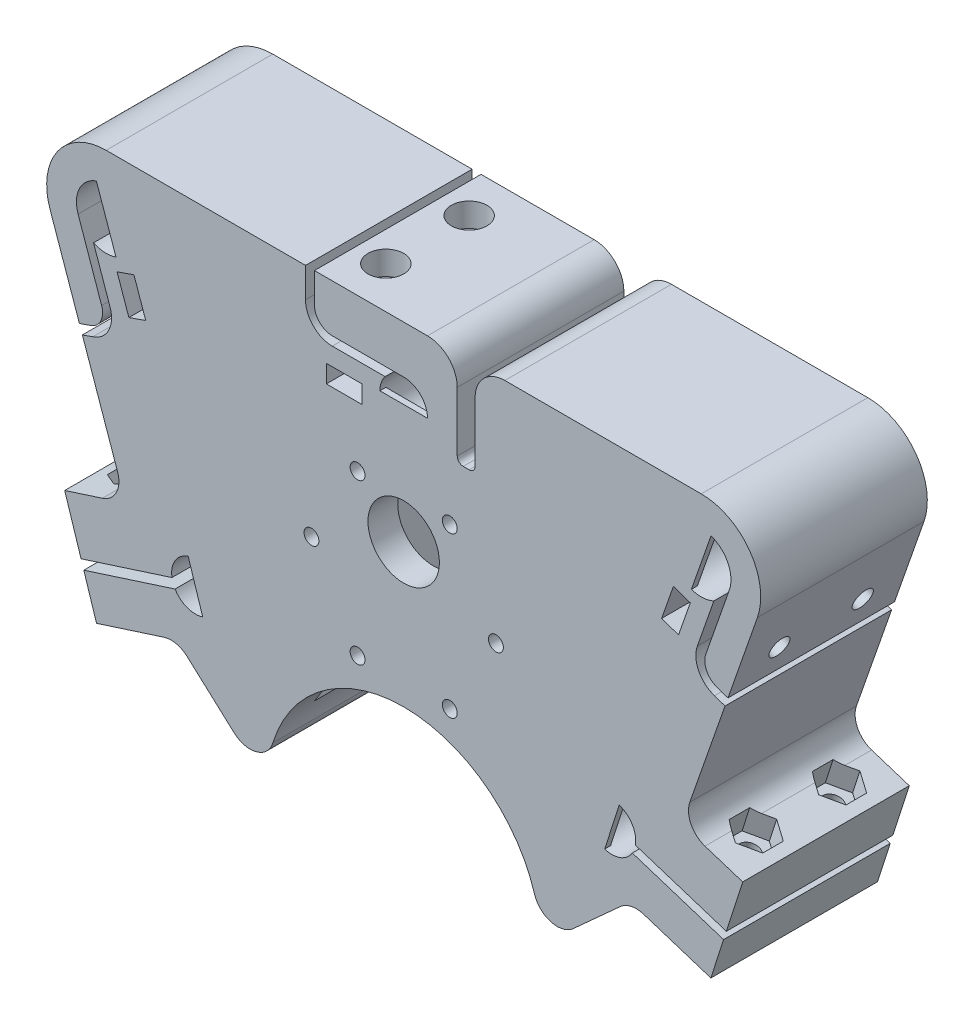
SolidWorks part; units mm, degrees
other "Uwaga1"
sketch "Szkic11" plane through (60, 10, 0) normal (0.4049, 0.0419, -0.9134) x (0.8662, -0.3375, 0.3685)
other "Uwaga2"
sketch "Szkic12" plane through (60, 10, 0) normal (0.4049, 0.0419, -0.9134) x (0.8662, -0.3375, 0.3685)
other "Uwaga3"
sketch "Szkic13"
ref_plane "Płaszczyzna przednia" through (0, 0, 0) normal (0, 0, 1) x (1, 0, 0)
ref_plane "Płaszczyzna górna" through (0, 0, 0) normal (0, 1, 0) x (1, 0, 0)
ref_plane "Płaszczyzna prawa" through (0, 0, 0) normal (1, 0, 0) x (0, 0, -1)
sketch "Szkic1" plane through (0, 0, 0) normal (0, 0, 1) x (1, 0, 0)
  line L0 (-50, 10) -> (4, 10)
  line L1 (-59.4412, -3.296) -> (-43.4971, -48.9664)
  line L2 (43.4971, -48.9664) -> (59.4412, -3.296)
  line L3 (-41.0394, -52.6727) -> (-23, -69)
  line L4 (23, -69) -> (41.0394, -52.6727)
  line L5 (38.4257, -48.0651) -> (43.2433, -49.6122)
  line L6 (38.9457, -46.6566) -> (43.7633, -48.2037)
  line L7 (0, -34.7604) -> (35, -46) construction
  line L8 (38.1168, -55.318) -> (51.621, -59.6546)
  line L9 (51.621, -59.6546) -> (53.7613, -52.9898)
  line L10 (53.7613, -52.9898) -> (43.2433, -49.6122)
  line L11 (43.7633, -48.2037) -> (54.2199, -51.5616)
  line L12 (54.2199, -51.5616) -> (56.9717, -42.9926)
  line L13 (56.9717, -42.9926) -> (46.7307, -39.704)
  line L14 (0, -29) -> (0, -114.3862) construction
  line L15 (0, 2) -> (-12, 2)
  line L16 (-3.1225, 0.5) -> (-12, 0.5)
  line L17 (-16.5, 5) -> (-16.5, 10)
  line L18 (-15, 5) -> (-15, 10)
  line L19 (9, 5) -> (9, -5)
  line L20 (10, -6) -> (11, -6)
  line L21 (12, -5) -> (12, 5)
  line L22 (17, 10) -> (50, 10)
  line L23 (-56.9717, -42.9926) -> (-46.7307, -39.704)
  line L24 (-54.2199, -51.5616) -> (-56.9717, -42.9926)
  line L25 (-43.7633, -48.2037) -> (-54.2199, -51.5616)
  line L26 (-38.9457, -46.6566) -> (-43.7633, -48.2037)
  line L27 (-38.4257, -48.0651) -> (-43.2433, -49.6122)
  line L28 (-53.7613, -52.9898) -> (-43.2433, -49.6122)
  line L29 (-51.621, -59.6546) -> (-53.7613, -52.9898)
  line L30 (-38.1168, -55.318) -> (-51.621, -59.6546)
  line L31 (-54.7206, -1.648) -> (-50.7653, -12.9775)
  line L32 (-52.1248, -4.5261) -> (-49.3471, -12.4823)
  line L33 (-52.6089, -16.7986) -> (-54.4971, -17.4578)
  line L34 (-52.2456, -18.2606) -> (-54.0027, -18.874)
  line L35 (54.7206, -1.648) -> (50.7653, -12.9775)
  line L36 (52.1248, -4.5261) -> (49.3471, -12.4823)
  line L37 (52.6089, -16.7986) -> (54.4971, -17.4578)
  line L38 (52.2456, -18.2606) -> (54.0027, -18.874)
  circle A0 centre (-50, 0) radius 5
  circle A1 centre (50, 0) radius 5
  circle A2 centre (-50, 0) radius 10
  circle A3 centre (50, 0) radius 10
  circle A4 centre (0, -2) radius 4
  circle A5 centre (0, -29) radius 15.5 construction
  circle A6 centre (0, -22) radius 6
  circle A7 centre (15.5, -29) radius 1.25
  circle A8 centre (7.75, -42.4234) radius 1.25
  circle A9 centre (-7.75, -42.4234) radius 1.25
  circle A10 centre (-15.5, -29) radius 1.25
  circle A11 centre (-7.75, -15.5766) radius 1.25
  circle A12 centre (7.75, -15.5766) radius 1.25
  circle A13 centre (-35, -46) radius 4
  circle A14 centre (35, -46) radius 4
  circle A15 centre (-35, -46) radius 9
  circle A16 centre (35, -46) radius 9
  arc A17 (23, -69) -> (-23, -69) centre (0, -69) ccw
  arc A19 (-12, 2) -> (-15, 5) centre (-12, 5) cw
  arc A20 (-12, 0.5) -> (-16.5, 5) centre (-12, 5) cw
  arc A21 (9, 5) -> (4, 10) centre (4, 5) ccw
  arc A22 (12, 5) -> (17, 10) centre (17, 5) cw
  arc A23 (11, -6) -> (12, -5) centre (11, -5) ccw
  arc A24 (9, -5) -> (10, -6) centre (10, -5) ccw
  arc A25 (-50.7653, -12.9775) -> (-52.6089, -16.7986) centre (-53.5977, -13.9663) cw
  arc A26 (-49.3471, -12.4823) -> (-52.2456, -18.2606) centre (-53.5977, -13.9663) cw
  arc A27 (49.3471, -12.4823) -> (52.2456, -18.2606) centre (53.5977, -13.9663) ccw
  arc A28 (50.7653, -12.9775) -> (52.6089, -16.7986) centre (53.5977, -13.9663) ccw
  point P32 (0, -29)
  point P78 (10.1421, 10)
  point P84 (10.1421, -2)
  point P87 (7.1421, -2)
  point P103 (-49.7765, -15.8098)
  dimension "D1" = 10
  dimension "D6" = 8
  dimension "D8" = 31
  dimension "D9" = 12
  dimension "D12" = 2.5
  dimension "D14" = 70
  dimension "D18" = 46
  dimension "D27" = 3
  dimension "D28" = 4.5
  dimension "D31" = 5
  dimension "D32" = 5
  dimension "D33" = 1
  dimension "D38" = 3
  dimension "D2" = 100
  dimension "D3" = 50
  dimension "D7" = 39
  dimension "D10" = 7
  dimension "D11" = 12
  dimension "D15" = 35
  dimension "D16" = 46
  dimension "D19" = 40
  dimension "D20" = 1.5
  dimension "D21" = 7
  dimension "D22" = 20
  dimension "D23" = 9
  dimension "D24" = 1.5
  dimension "D25" = 1.5
  dimension "D26" = 15
  dimension "D29" = 3
  dimension "D30" = 16
  dimension "D34" = 9
  dimension "D35" = 15
  dimension "D36" = 1.5021
  dimension "D37" = 1.5
  dimension "D4" = 5
  dimension "D5" = 5
  dimension "D17" = 5
  dimension "D13" = 6
extrude "Dodanie-wyciągnięcie1" add sketch "Szkic1" along normal blind 28 contours A2 A0 | A17 L4 A16 L2 A3 L0 A2 L1 A15 L3 A12 A11 A10 A9 A8 A7 A6 A4 | A3 A1 | A16 A14 | A15 A13 | A16 L4 L8 L9 L10 | L12 L13 L2 L11 | A15 L28 L29 L30 L3 | L25 L1 L23 L24 | A25 L31 A2 L1 L33 | L35 A28 L37 L2 A3 region at (-33.25, 8.6619, 0) region at (-43.1289, 6.8711, 0) region at (-54.1165, -12.2056, 0) region at (-50.4165, -45.6303, 0) region at (-36.0734, -37.3207, 0) region at (-46.741, -54.5771, 0) region at (56.8711, 6.8711, 0) region at (46.741, -54.5771, 0) region at (54.1165, -12.2056, 0) region at (27.0061, -42.4532, 0) region at (50.4165, -45.6303, 0)
fillet "Zaokrąglenie1" radius 4 6 edges at (-46.7307, -39.704, 14) (-38.1168, -55.318, 14) (-23, -69, 14) (23, -69, 14) (38.1168, -55.318, 14) (46.7307, -39.704, 14)
sketch "Szkic2" plane through (12.5403, -39.0504, 0) normal (0.3058, -0.9521, 0) x (0.9521, 0.3058, 0)
  line L0 (-55.5122, 28) -> (-67.3885, 28) construction
  line L1 (-67.3885, 28) -> (-67.3885, 0) construction
  circle A0 centre (-62.3885, 21) radius 1.7
  circle A1 centre (-62.3885, 7) radius 1.7
  dimension "D1" = 14
  dimension "D4" = 3.4
  dimension "D2" = 7
  dimension "D3" = 5
extrude "Wytnij-wyciągnięcie1" cut sketch "Szkic2" against normal through all
sketch "Szkic3" plane through (12.5403, -39.0504, 0) normal (0.3058, -0.9521, 0) x (0.9521, 0.3058, 0)
  circle A0 centre (-62.3885, 21) radius 3
  circle A1 centre (-62.3885, 7) radius 3
  dimension "D1" = 6
extrude "Wytnij-wyciągnięcie2" cut sketch "Szkic3" against normal blind 3
sketch "Szkic4" plane through (7.1896, -22.3885, 0) normal (-0.3058, 0.9521, 0) x (0.9521, 0.3058, 0)
  line L1 (-62.3885, -24.4641) -> (-59.3885, -22.7321)
  line L2 (-59.3885, -22.7321) -> (-59.3885, -19.2679)
  line L3 (-59.3885, -19.2679) -> (-62.3885, -17.5359)
  line L4 (-62.3885, -17.5359) -> (-65.3885, -19.2679)
  line L5 (-65.3885, -19.2679) -> (-65.3885, -22.7321)
  line L6 (-65.3885, -22.7321) -> (-62.3885, -24.4641)
  line L7 (-62.3885, -10.4641) -> (-59.3885, -8.7321)
  line L8 (-59.3885, -8.7321) -> (-59.3885, -5.2679)
  line L9 (-59.3885, -5.2679) -> (-62.3885, -3.5359)
  line L10 (-62.3885, -3.5359) -> (-65.3885, -5.2679)
  line L11 (-65.3885, -5.2679) -> (-65.3885, -8.7321)
  line L12 (-65.3885, -8.7321) -> (-62.3885, -10.4641)
  circle A0 centre (-62.3885, -21) radius 3 construction
  circle A1 centre (-62.3885, -7) radius 3 construction
  dimension "D1" = 6
extrude "Wytnij-wyciągnięcie3" cut sketch "Szkic4" against normal blind 4 and the other way blind 4
sketch "Szkic5" plane through (-54.0092, -18.8553, 0) normal (-0.9441, -0.3296, 0) x (0, 0, 1)
  line L0 (28, 16.4802) -> (28, 1.4802) construction
  line L1 (28, 1.4802) -> (0, 1.4802) construction
  circle A0 centre (21, 6.4802) radius 1.7
  circle A1 centre (7, 6.4802) radius 1.7
  dimension "D1" = 14
  dimension "D2" = 3.4
  dimension "D3" = 7
  dimension "D4" = 5
extrude "Wytnij-wyciągnięcie4" cut sketch "Szkic5" against normal blind 10
sketch "Szkic6" plane through (-54.0092, -18.8553, 0) normal (-0.9441, -0.3296, 0) x (0, 0, 1)
  line L0 (22.7321, 9.4802) -> (28, 9.4802)
  line L1 (24.4641, 6.4802) -> (22.7321, 9.4802)
  line L2 (22.7321, 9.4802) -> (19.2679, 9.4802)
  line L3 (19.2679, 9.4802) -> (17.5359, 6.4802)
  line L4 (17.5359, 6.4802) -> (19.2679, 3.4802)
  line L5 (19.2679, 3.4802) -> (22.7321, 3.4802)
  line L6 (22.7321, 3.4802) -> (24.4641, 6.4802)
  line L7 (10.4641, 6.4802) -> (8.7321, 9.4802)
  line L8 (8.7321, 9.4802) -> (5.2679, 9.4802)
  line L9 (5.2679, 9.4802) -> (3.5359, 6.4802)
  line L10 (3.5359, 6.4802) -> (5.2679, 3.4802)
  line L11 (5.2679, 3.4802) -> (8.7321, 3.4802)
  line L12 (8.7321, 3.4802) -> (10.4641, 6.4802)
  line L13 (28, 16.4802) -> (28, 1.4802) construction
  line L14 (28, 9.4802) -> (28, 3.4802)
  line L15 (28, 3.4802) -> (22.7321, 3.4802)
  line L16 (5.2679, 9.4802) -> (0, 9.4802)
  line L17 (0, 16.4802) -> (0, 1.4802) construction
  line L18 (0, 9.4802) -> (0, 3.4802)
  line L19 (0, 3.4802) -> (5.2679, 3.4802)
  circle A0 centre (21, 6.4802) radius 3 construction
  circle A1 centre (7, 6.4802) radius 3 construction
  circle M2 centre (21, 6.4802) radius 1.7
  circle M3 centre (7, 6.4802) radius 1.7
  line M4 (0, 16.4802) -> (0, 1.4802)
  line M6 (28, 1.4802) -> (28, 16.4802)
  dimension "D1" = 6
extrude "Wytnij-wyciągnięcie5" cut sketch "Szkic6" against normal blind 3 from offset 9.5 contours L5 L6 L1 L2 L3 L4 M2 | L15 L0 L1 L6 M6 | L19 L10 L9 L16 M4 | L11 L12 L7 L8 L9 L10 M3 | M2 | M3 region at (-56.1452, -12.7372, 25.7706) region at (-56.6245, -11.3643, 23.5187) region at (-55.6658, -14.1101, 9.5187) region at (-56.1452, -12.7372, 2.2294) region at (-56.1452, -12.7372, 21) region at (-56.1452, -12.7372, 7) offset against normal yes
mirror "Lustro1" about plane through (0, 0, 0) normal (1, 0, 0) of "Wytnij-wyciągnięcie5", "Wytnij-wyciągnięcie4", "Wytnij-wyciągnięcie2", "Wytnij-wyciągnięcie1", "Wytnij-wyciągnięcie3"
sketch "Szkic7" plane through (0, 10, 0) normal (0, 1, 0) x (1, 0, 0)
  line L0 (-15, 0) -> (4, 0) construction
  line L1 (-15, -28) -> (-15, 0) construction
  circle A0 centre (-10, -21) radius 1.7
  circle A1 centre (-10, -7) radius 1.7
  point P4 (0, 0)
  point P5 (0, 0)
  point P6 (0, 0)
  dimension "D1" = 3.4
  dimension "D2" = 14
  dimension "D3" = 7
  dimension "D4" = 5
extrude "Wytnij-wyciągnięcie6" cut sketch "Szkic7" against normal blind 14
sketch "Szkic8" plane through (0, 10, 0) normal (0, 1, 0) x (1, 0, 0)
  line L0 (-7, -22.7321) -> (-7, -28)
  line L1 (-10, -24.4641) -> (-7, -22.7321)
  line L2 (-7, -22.7321) -> (-7, -19.2679)
  line L3 (-7, -19.2679) -> (-10, -17.5359)
  line L4 (-10, -17.5359) -> (-13, -19.2679)
  line L5 (-13, -19.2679) -> (-13, -22.7321)
  line L6 (-13, -22.7321) -> (-10, -24.4641)
  line L7 (-10, -10.4641) -> (-7, -8.7321)
  line L8 (-7, -8.7321) -> (-7, -5.2679)
  line L9 (-7, -5.2679) -> (-10, -3.5359)
  line L10 (-10, -3.5359) -> (-13, -5.2679)
  line L11 (-13, -5.2679) -> (-13, -8.7321)
  line L12 (-13, -8.7321) -> (-10, -10.4641)
  line L13 (-15, -28) -> (4, -28) construction
  line L14 (-7, -28) -> (-13, -28)
  line L15 (-13, -28) -> (-13, -22.7321)
  line L16 (-7, -5.2679) -> (-7, 0)
  line L17 (-15, 0) -> (4, 0) construction
  line L18 (-7, 0) -> (-13, 0)
  line L19 (-13, 0) -> (-13, -5.2679)
  circle A0 centre (-10, -21) radius 3 construction
  circle A1 centre (-10, -7) radius 3 construction
  circle M1 centre (-10, -21) radius 1.7
  circle M2 centre (-10, -7) radius 1.7
  line M3 (4, 0) -> (-15, 0)
  line M5 (-15, -28) -> (4, -28)
  dimension "D1" = 6
extrude "Wytnij-wyciągnięcie7" cut sketch "Szkic8" against normal blind 3 from offset 12.5 contours L5 L6 L1 L2 L3 L4 M1 | M1 | L15 L0 L1 L6 M5 | M2 | L11 L12 L7 L8 L9 L10 M2 | L19 L10 L9 L16 M3 region at (-10, 10, 25.7706) region at (-8.5458, 10, 23.5187) region at (-11.4542, 10, 9.5187) region at (-10, 10, 2.2294) region at (-10, 10, 21) region at (-10, 10, 7) offset against normal yes
sketch "Szkic9" plane through (0, 0, 28) normal (0, 0, 1) x (1, 0, 0)
  line L0 (-36.223, -42.1916) -> (-33.777, -49.8084)
  line L1 (36.223, -42.1916) -> (33.777, -49.8084)
  line L2 (-51.648, 4.7206) -> (-48.352, -4.7206)
  line L3 (51.648, 4.7206) -> (48.352, -4.7206)
  line L4 (-4, -2) -> (4, -2)
  line L36 (-36.4063, -56.8662) -> (-28.4915, -64.0297)
  line L37 (28.4915, -64.0297) -> (36.4063, -56.8662)
  line L38 (40.3135, -56.0234) -> (51.621, -59.6546)
  line L39 (51.621, -59.6546) -> (53.7613, -52.9898)
  line L40 (53.7613, -52.9898) -> (38.4257, -48.0651)
  line L41 (38.9457, -46.6566) -> (54.2199, -51.5616)
  line L42 (54.2199, -51.5616) -> (56.9717, -42.9926)
  line L43 (56.9717, -42.9926) -> (50.6362, -40.9581)
  line L44 (48.0827, -35.8313) -> (54.0027, -18.874)
  line L45 (54.0027, -18.874) -> (52.2456, -18.2606)
  line L46 (49.3471, -12.4823) -> (52.1248, -4.5261)
  line L47 (54.7206, -1.648) -> (50.7653, -12.9775)
  line L48 (52.6089, -16.7986) -> (54.4971, -17.4578)
  line L49 (54.4971, -17.4578) -> (59.4412, -3.296)
  line L50 (50, 10) -> (17, 10)
  line L51 (12, 5) -> (12, -5)
  line L52 (11, -6) -> (10, -6)
  line L53 (9, -5) -> (9, 5)
  line L54 (4, 10) -> (-15, 10)
  line L55 (-15, 10) -> (-15, 5)
  line L56 (-12, 2) -> (0, 2)
  line L57 (-3.1225, 0.5) -> (-12, 0.5)
  line L58 (-16.5, 5) -> (-16.5, 10)
  line L59 (-16.5, 10) -> (-50, 10)
  line L60 (-59.4412, -3.296) -> (-54.4971, -17.4578)
  line L61 (-54.4971, -17.4578) -> (-52.6089, -16.7986)
  line L62 (-50.7653, -12.9775) -> (-54.7206, -1.648)
  line L63 (-52.1248, -4.5261) -> (-49.3471, -12.4823)
  line L64 (-52.2456, -18.2606) -> (-54.0027, -18.874)
  line L65 (-54.0027, -18.874) -> (-48.0827, -35.8313)
  line L66 (-50.6362, -40.9581) -> (-56.9717, -42.9926)
  line L67 (-56.9717, -42.9926) -> (-54.2199, -51.5616)
  line L68 (-54.2199, -51.5616) -> (-38.9457, -46.6566)
  line L69 (-38.4257, -48.0651) -> (-53.7613, -52.9898)
  line L70 (-53.7613, -52.9898) -> (-51.621, -59.6546)
  line L71 (-51.621, -59.6546) -> (-40.3135, -56.0234)
  line L72 (-36.4063, -56.8662) -> (-28.4915, -64.0297)
  line L73 (28.4915, -64.0297) -> (36.4063, -56.8662)
  line L74 (40.3135, -56.0234) -> (51.621, -59.6546)
  line L75 (51.621, -59.6546) -> (53.7613, -52.9898)
  line L76 (53.7613, -52.9898) -> (38.4257, -48.0651)
  line L77 (38.9457, -46.6566) -> (54.2199, -51.5616)
  line L78 (54.2199, -51.5616) -> (56.9717, -42.9926)
  line L79 (56.9717, -42.9926) -> (50.6362, -40.9581)
  line L80 (48.0827, -35.8313) -> (54.0027, -18.874)
  line L81 (54.0027, -18.874) -> (52.2456, -18.2606)
  line L82 (49.3471, -12.4823) -> (52.1248, -4.5261)
  line L83 (54.7206, -1.648) -> (50.7653, -12.9775)
  line L84 (52.6089, -16.7986) -> (54.4971, -17.4578)
  line L85 (54.4971, -17.4578) -> (59.4412, -3.296)
  line L86 (50, 10) -> (17, 10)
  line L87 (12, 5) -> (12, -5)
  line L88 (11, -6) -> (10, -6)
  line L89 (9, -5) -> (9, 5)
  line L90 (4, 10) -> (-15, 10)
  line L91 (-15, 10) -> (-15, 5)
  line L92 (-12, 2) -> (0, 2)
  line L93 (-3.1225, 0.5) -> (-12, 0.5)
  line L94 (-16.5, 5) -> (-16.5, 10)
  line L95 (-16.5, 10) -> (-50, 10)
  line L96 (-59.4412, -3.296) -> (-54.4971, -17.4578)
  line L97 (-54.4971, -17.4578) -> (-52.6089, -16.7986)
  line L98 (-50.7653, -12.9775) -> (-54.7206, -1.648)
  line L99 (-52.1248, -4.5261) -> (-49.3471, -12.4823)
  line L100 (-52.2456, -18.2606) -> (-54.0027, -18.874)
  line L101 (-54.0027, -18.874) -> (-48.0827, -35.8313)
  line L102 (-50.6362, -40.9581) -> (-56.9717, -42.9926)
  line L103 (-56.9717, -42.9926) -> (-54.2199, -51.5616)
  line L104 (-54.2199, -51.5616) -> (-38.9457, -46.6566)
  line L105 (-38.4257, -48.0651) -> (-53.7613, -52.9898)
  line L106 (-53.7613, -52.9898) -> (-51.621, -59.6546)
  line L107 (-51.621, -59.6546) -> (-40.3135, -56.0234)
  arc A24 (-28.4915, -64.0297) -> (-21.984, -62.2397) centre (-25.8074, -61.064) ccw
  arc A25 (21.984, -62.2397) -> (-21.984, -62.2397) centre (0, -69) ccw
  arc A26 (21.984, -62.2397) -> (28.4915, -64.0297) centre (25.8074, -61.064) ccw
  arc A27 (40.3135, -56.0234) -> (36.4063, -56.8662) centre (39.0904, -59.8318) ccw
  arc A28 (38.9457, -46.6566) -> (38.4257, -48.0651) centre (35, -46) ccw
  arc A29 (48.0827, -35.8313) -> (50.6362, -40.9581) centre (51.8592, -37.1497) ccw
  arc A30 (49.3471, -12.4823) -> (52.2456, -18.2606) centre (53.5977, -13.9663) ccw
  arc A31 (54.7206, -1.648) -> (52.1248, -4.5261) centre (50, 0) ccw
  arc A32 (50.7653, -12.9775) -> (52.6089, -16.7986) centre (53.5977, -13.9663) ccw
  arc A33 (59.4412, -3.296) -> (50, 10) centre (50, 0) ccw
  arc A34 (17, 10) -> (12, 5) centre (17, 5) ccw
  arc A35 (11, -6) -> (12, -5) centre (11, -5) ccw
  arc A36 (9, -5) -> (10, -6) centre (10, -5) ccw
  arc A37 (9, 5) -> (4, 10) centre (4, 5) ccw
  arc A38 (-15, 5) -> (-12, 2) centre (-12, 5) ccw
  arc A39 (-3.1225, 0.5) -> (0, 2) centre (0, -2) ccw
  arc A40 (-16.5, 5) -> (-12, 0.5) centre (-12, 5) ccw
  arc A41 (-50, 10) -> (-59.4412, -3.296) centre (-50, 0) ccw
  arc A42 (-52.6089, -16.7986) -> (-50.7653, -12.9775) centre (-53.5977, -13.9663) ccw
  arc A43 (-52.1248, -4.5261) -> (-54.7206, -1.648) centre (-50, 0) ccw
  arc A44 (-52.2456, -18.2606) -> (-49.3471, -12.4823) centre (-53.5977, -13.9663) ccw
  arc A45 (-50.6362, -40.9581) -> (-48.0827, -35.8313) centre (-51.8592, -37.1497) ccw
  arc A46 (-38.4257, -48.0651) -> (-38.9457, -46.6566) centre (-35, -46) ccw
  arc A47 (-36.4063, -56.8662) -> (-40.3135, -56.0234) centre (-39.0904, -59.8318) ccw
  arc A48 (-28.4915, -64.0297) -> (-21.984, -62.2397) centre (-25.8074, -61.064) ccw
  arc A49 (21.984, -62.2397) -> (-21.984, -62.2397) centre (0, -69) ccw
  arc A50 (21.984, -62.2397) -> (28.4915, -64.0297) centre (25.8074, -61.064) ccw
  arc A51 (40.3135, -56.0234) -> (36.4063, -56.8662) centre (39.0904, -59.8318) ccw
  arc A52 (38.9457, -46.6566) -> (38.4257, -48.0651) centre (35, -46) ccw
  arc A53 (48.0827, -35.8313) -> (50.6362, -40.9581) centre (51.8592, -37.1497) ccw
  arc A54 (49.3471, -12.4823) -> (52.2456, -18.2606) centre (53.5977, -13.9663) ccw
  arc A55 (54.7206, -1.648) -> (52.1248, -4.5261) centre (50, 0) ccw
  arc A56 (50.7653, -12.9775) -> (52.6089, -16.7986) centre (53.5977, -13.9663) ccw
  arc A57 (59.4412, -3.296) -> (50, 10) centre (50, 0) ccw
  arc A58 (17, 10) -> (12, 5) centre (17, 5) ccw
  arc A59 (11, -6) -> (12, -5) centre (11, -5) ccw
  arc A60 (9, -5) -> (10, -6) centre (10, -5) ccw
  arc A61 (9, 5) -> (4, 10) centre (4, 5) ccw
  arc A62 (-15, 5) -> (-12, 2) centre (-12, 5) ccw
  arc A63 (-3.1225, 0.5) -> (0, 2) centre (0, -2) ccw
  arc A64 (-16.5, 5) -> (-12, 0.5) centre (-12, 5) ccw
  arc A65 (-50, 10) -> (-59.4412, -3.296) centre (-50, 0) ccw
  arc A66 (-52.6089, -16.7986) -> (-50.7653, -12.9775) centre (-53.5977, -13.9663) ccw
  arc A67 (-52.1248, -4.5261) -> (-54.7206, -1.648) centre (-50, 0) ccw
  arc A68 (-52.2456, -18.2606) -> (-49.3471, -12.4823) centre (-53.5977, -13.9663) ccw
  arc A69 (-50.6362, -40.9581) -> (-48.0827, -35.8313) centre (-51.8592, -37.1497) ccw
  arc A70 (-38.4257, -48.0651) -> (-38.9457, -46.6566) centre (-35, -46) ccw
  arc A71 (-36.4063, -56.8662) -> (-40.3135, -56.0234) centre (-39.0904, -59.8318) ccw
  dimension "D1" = 0
extrude "Dodanie-wyciągnięcie2" add sketch "Szkic9" against normal blind 1 contours L2 A67 | L4 A63 | L3 A55 | L1 A52 | L0 A70 region at (-33.3836, -45.4809, 28) region at (-47.9965, 0.6994, 28) region at (33.3836, -45.4809, 28) region at (0, -3.6977, 28) region at (47.9965, 0.6994, 28)
sketch "Szkic10" plane through (0, 0, 0) normal (0, 0, -1) x (-1, 0, 0)
  line L0 (7.75, -42.4234) -> (-7.75, -15.5766) construction
  line L1 (-7.75, -15.5766) -> (-15.5, -29) construction
  line L2 (-15.5, -29) -> (15.5, -29) construction
  line L3 (20, -29) -> (20, -58.8701)
  line L4 (-20, -29) -> (-20, -58.8701)
  line L5 (-20, -58.8701) -> (20, -58.8701)
  circle A0 centre (-7.75, -15.5766) radius 1.25 construction
  circle A1 centre (7.75, -42.4234) radius 1.25 construction
  circle A2 centre (-15.5, -29) radius 1.25 construction
  circle A3 centre (15.5, -29) radius 1.25 construction
  circle A4 centre (-7.75, -15.5766) radius 1.25 construction
  circle A5 centre (7.75, -42.4234) radius 1.25 construction
  circle A6 centre (-15.5, -29) radius 1.25 construction
  circle A7 centre (15.5, -29) radius 1.25 construction
  circle A8 centre (0, -29) radius 20
  dimension "D1" = 40
extrude "Wytnij-wyciągnięcie8" cut sketch "Szkic10" against normal blind 23 contours A8 L4 L5 L3 | A8 region at (0, -29, 0) region at (0, -51.0855, 0)
sketch "Szkic14" plane through (0, 10, 0) normal (0, 1, 0) x (1, 0, 0)
  circle A0 centre (-10, -7) radius 3
  circle A1 centre (-10, -21) radius 3
  dimension "D1" = 6
extrude "Wytnij-wyciągnięcie9" cut sketch "Szkic14" against normal blind 4
